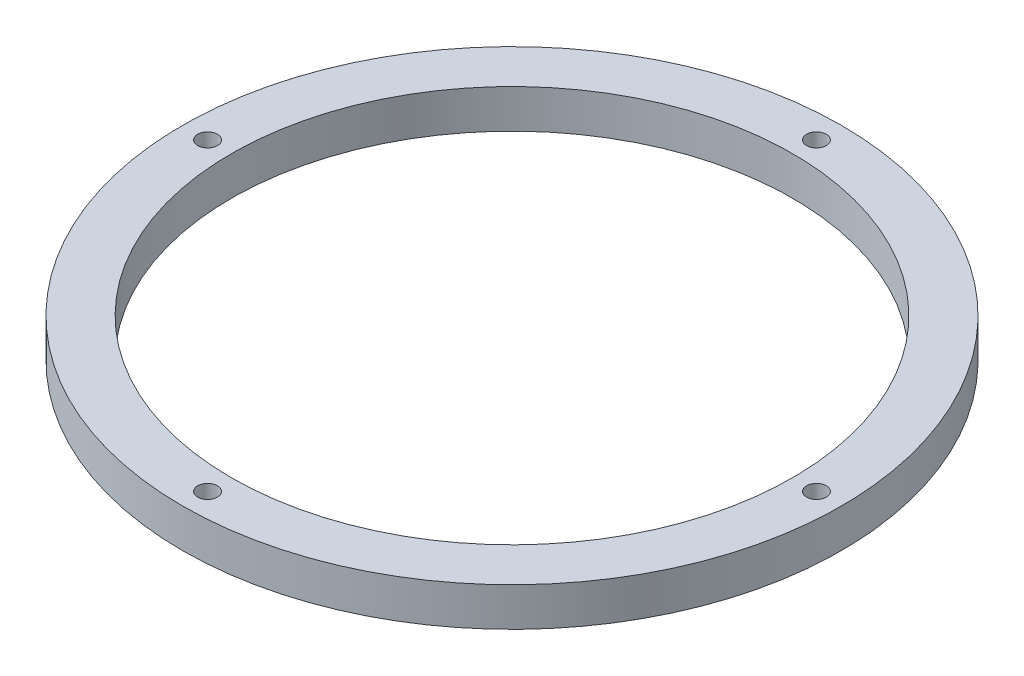
SolidWorks part; units mm, degrees
ref_plane "Front Plane" through (0, 0, 0) normal (0, 0, 1) x (1, 0, 0)
ref_plane "Top Plane" through (0, 0, 0) normal (0, 1, 0) x (1, 0, 0)
ref_plane "Right Plane" through (0, 0, 0) normal (1, 0, 0) x (0, 0, -1)
sketch "Sketch1" plane through (0, 0, 0) normal (0, 1, 0) x (1, 0, 0)
  circle A0 centre (0, 0) radius 85.25
  circle A5 centre (0, 0) radius 72.6
  dimension "D1" = 170.5
  dimension "D2" = 145.2
extrude "Boss-Extrude1" add sketch "Sketch1" along normal mid plane 10
sketch "Sketch2" plane through (0, 0, 0) normal (0, 1, 0) x (1, 0, 0)
  circle A0 centre (-78.75, 0) radius 1.27
  dimension "D2" = 2.54
  dimension "D1" = 78.75
extrude "Cut-Extrude1" cut sketch "Sketch2" against normal through all both and the other way through all
ref_axis "Axis1" through (0, 5.5, 0) along (0, -1, 0)
pattern_circular "CirPattern1" count 4 over 360 about axis through (0, 5.5, 0) along (0, -1, 0) of "Cut-Extrude1"
hole_wizard "CSK for #10 Flat Head Machine Screw (100)1" positions "3DSketch1" profile "Sketch3" countersink size "#10" standard "ANSI Inch" end condition through all
sketch3d "3DSketch1"
  line L0 (78.75, -5, 0) -> (78.75, 5, 0) construction
  line L1 (0, -5, -78.75) -> (0, 5, -78.75) construction
  line L2 (-78.75, -5, 0) -> (-78.75, 5, 0) construction
  line L3 (0, -5, 78.75) -> (0, 5, 78.75) construction
  point P0 (78.75, -5, 0)
  point P4 (0, -5, -78.75)
  point P8 (-78.75, -5, 0)
  point P12 (0, -5, 78.75)
sketch "Sketch3" plane through (78.75, -5, 0) normal (1, 0, 0) x (0, 0, -1)
  line L0 (0, 0) -> (0, 10)
  line L1 (0, 10) -> (2.5527, 10)
  line L2 (2.5527, 10) -> (2.5527, 1.9608)
  line L3 (2.5527, 1.9608) -> (4.8895, 0)
  line L5 (4.8895, 0) -> (0, 0)
  line L6 (-2.5527, 1.9608) -> (-4.8895, 0) construction
  line L11 (0, -6.35) -> (0, 107.95) construction
  dimension "Thru Hole Dia." = 5.1054
  dimension "Thru Hole Depth" = 10
  dimension "Near C'Sink Dia." = 9.779
  dimension "Near C'Sink Angle" = 100
equation "\"thicknes\"= 10mm"
equation "\"D1@Boss-Extrude1\"=\"thicknes\""
equation "\"id\" = 145.2mm"
equation "\"D2@Sketch1\"=\"id\""
equation "\"od\" = 170.5mm"
equation "\"D1@Sketch1\"=\"od\""
equation "\"hole_radius\"= \"hole_diameter\" / 2"
equation "\"D1@Sketch2\"=\"hole_radius\""
equation "\"hole_diameter\"= 157.5mm"
